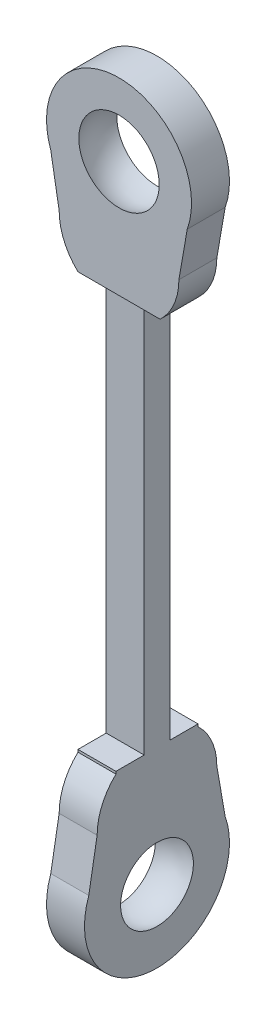
SolidWorks part; units mm, degrees
ref_plane "前视基准面" through (0, 0, 0) normal (0, 0, 1) x (1, 0, 0)
ref_plane "上视基准面" through (0, 0, 0) normal (0, 1, 0) x (1, 0, 0)
ref_plane "右视基准面" through (0, 0, 0) normal (1, 0, 0) x (0, 0, -1)
other "Configuration Table"
sketch "草图1" plane through (0, 0, 0) normal (0, 0, 1) x (1, 0, 0)
  circle A0 centre (0, 0) radius 2.165
  circle A1 centre (0, 0) radius 3.532
extrude "凸台-拉伸1" add sketch "草图1" along normal blind 2.849
sketch "草图3" plane through (0, 0, 2.849) normal (0, 0, 1) x (1, 0, 0)
  line L0 (-2.916, -3.532) -> (-3.532, 0)
  line L1 (2.916, -3.532) -> (3.532, 0)
  arc A0 (2.656, -2.3283) -> (3.3235, -1.1956) centre (0, 0) ccw
  arc A1 (-2.916, -3.532) -> (2.916, -3.532) centre (0, -3.532) ccw
  arc A2 (3.532, 0) -> (-3.532, 0) centre (0, 0) ccw
  circle M4 centre (0, 0) radius 3.532
extrude "凸台-拉伸3" add sketch "草图3" against normal up to surface (2.849 mm away) contours L0 A1 L1 M4 region at (0, -4.4115, 2.849) up to face at (3.532, 0, 0)
sketch "草图4" plane through (0, 0, 2.849) normal (0, 0, 1) x (1, 0, 0)
  line L0 (0, 0) -> (0, -15.25)
  line L1 (0, -6.448) -> (2, -6.448)
  line L2 (0, -6.448) -> (-2, -6.448)
  line L3 (-2, -6.448) -> (-2, -5.654)
  line L4 (2, -6.448) -> (2, -5.654)
  arc A0 (-2.916, -3.532) -> (2.916, -3.532) centre (0, -3.532) ccw construction
  arc A1 (-2, -5.654) -> (0, -6.448) centre (0, -3.532) ccw
  arc A2 (2, -5.654) -> (0, -6.448) centre (0, -3.532) cw
  arc M6 (-2.916, -3.532) -> (2.916, -3.532) centre (0, -3.532) ccw
extrude "凸台-拉伸4" add sketch "草图4" against normal up to surface (2.849 mm away) contours L1 L4 M6 | L2 L3 A1 region at (1.5146, -6.2166, 2.849) up to face at (0, -1.9109, 0)
sketch "草图5" plane through (0, 0, 2.849) normal (0, 0, 1) x (1, 0, 0)
  line L0 (-2, -6.448) -> (2, -6.448)
  line L1 (-2, -6.448) -> (-2, -15.25)
  line L2 (-2, -15.25) -> (2, -15.25)
  line L3 (2, -6.448) -> (2, -15.25)
extrude "凸台-拉伸5" add sketch "草图5" against normal up to surface (2.849 mm away) up to face at (0, -3.6401, 0)
ref_plane "基准面1" through (-12, 0, 0) normal (-1, 0, 0) x (0, 0, 1)
sketch "草图9" plane through (0, -15.25, 0) normal (0, -1, 0) x (1, 0, 0)
  circle A0 centre (0, 1.4245) radius 0.3861
ref_plane "基准面2" through (0, 0, 0) normal (-1, 0, 0) x (0, 0, 1)
sketch "草图11" plane through (0, 0, 0) normal (-1, 0, 0) x (0, 0, 1)
  line L0 (4.748, -29.3044) -> (4.3405, -26.968)
  line L1 (3.4245, -24.846) -> (3.4245, -15.25)
  line L2 (3.4245, -15.25) -> (-0.5755, -15.25)
  line L3 (-0.5755, -15.25) -> (-0.5755, -24.846)
  line L4 (-1.4915, -26.968) -> (-1.899, -29.3044)
  circle A0 centre (1.4245, -30.5) radius 2.165
  arc A1 (-1.899, -29.3044) -> (4.748, -29.3044) centre (1.4245, -30.5) ccw
  arc A2 (4.3405, -26.968) -> (3.4245, -24.846) centre (1.4245, -26.968) ccw
  arc A3 (-0.5755, -24.846) -> (-1.4915, -26.968) centre (1.4245, -26.968) ccw
extrude "凸台-拉伸6" add sketch "草图11" along normal blind 2 and the other way blind 2
sketch "草图12" plane through (-12, 0, 0) normal (-1, 0, 0) x (0, 0, 1)
  line L0 (0.5, 4.1241) -> (0.5, -15.2363)
  line L9 (0, -5.654) -> (0, -15.25) construction
  line L10 (0.5, -15.2363) -> (-0.8762, -15.2363)
  line L11 (-0.8762, -15.2363) -> (-0.8762, 4.1241)
  line L12 (-0.8762, 4.1241) -> (0.5, 4.1241)
  line L13 (2.349, 4.1241) -> (2.349, -15.2363)
  line L14 (2.349, -15.2363) -> (3.4441, -15.2363)
  line L15 (2.849, -15.25) -> (2.849, -5.654) construction
  line L16 (2.349, 4.1241) -> (3.4441, 4.1241)
  line L17 (3.4441, 4.1241) -> (3.4441, -15.2363)
  dimension "D1" = 0.5
  dimension "D2" = 0.5
extrude "切除-拉伸1" cut sketch "草图12" against normal blind 24
sketch "草图14" plane through (0, 0, 3.4245) normal (0, 0, 1) x (1, 0, 0)
  line L0 (-1.5, -15.25) -> (-1.5, -35.1595)
  line L1 (2, -15.25) -> (-2, -15.25) construction
  line L2 (-2, -24.846) -> (-2, -15.25) construction
  line L3 (-1.5, -15.25) -> (-3.435, -15.25)
  line L4 (-3.435, -15.25) -> (-3.435, -35.1595)
  line L5 (-3.435, -35.1595) -> (-1.5, -35.1595)
  line L6 (1.5, -15.25) -> (1.5, -35.1595)
  line L7 (2, -24.846) -> (2, -15.25) construction
  line L8 (1.5, -15.25) -> (3.4686, -15.25)
  line L9 (3.4686, -15.25) -> (3.4686, -35.1595)
  line L10 (3.4686, -35.1595) -> (1.5, -35.1595)
  dimension "D1" = 0.5
  dimension "D2" = 0.5
extrude "切除-拉伸2" cut sketch "草图14" against normal blind 24 and the other way blind 24
sketch "草图15" plane through (-12, 0, 0) normal (-1, 0, 0) x (0, 0, 1)
  line L0 (0.8, -5.654) -> (0.8, -24.7275)
  line L1 (0.5, -5.654) -> (2.349, -5.654) construction
  line L2 (0.8, -24.7275) -> (-1.8291, -24.7275)
  line L3 (-1.8291, -24.7275) -> (-1.8291, -5.654)
  line L4 (-1.8291, -5.654) -> (0.8, -5.654)
  line L5 (0.5, -5.654) -> (0.5, -15.2363) construction
  line L6 (2.049, -5.654) -> (2.049, -24.7275)
  line L7 (2.049, -24.7275) -> (5.2703, -24.7275)
  line L8 (5.2703, -24.7275) -> (5.2703, -5.654)
  line L9 (5.2703, -5.654) -> (2.049, -5.654)
  line L10 (2.349, -15.2363) -> (2.349, -5.654) construction
  dimension "D1" = 0.3
  dimension "D2" = 0.3
extrude "切除-拉伸3" cut sketch "草图15" against normal blind 24
sketch "草图16" plane through (0, 0, 0.8) normal (0, 0, -1) x (-1, 0, 0)
  line L0 (-1.5, -15.25) -> (-2, -15.25)
  line L1 (-2, -15.25) -> (-2, -5.654)
  line L2 (-2, -5.654) -> (-1.5, -5.654)
  line L3 (-2, -5.654) -> (2, -5.654) construction
  line L4 (-1.5, -5.654) -> (-1.5, -15.25)
  line L5 (1.5, -15.25) -> (1.5, -5.654)
  line L6 (1.5, -5.654) -> (2, -5.654)
  line L7 (2, -5.654) -> (2, -15.25)
  line L8 (2, -5.654) -> (2, -15.25) construction
  line L9 (1.5, -15.25) -> (2, -15.25) construction
  line L10 (2, -15.25) -> (1.5, -15.25)
extrude "切除-拉伸4" cut sketch "草图16" against normal blind 24
sketch "草图17" plane through (0, 0, 2.049) normal (0, 0, 1) x (1, 0, 0)
  line L0 (-0.925, -5.654) -> (-0.925, -35.9981)
  line L1 (-2, -5.654) -> (2, -5.654) construction
  line L2 (-1.5, -5.654) -> (-1.5, -24.7275) construction
  line L3 (-0.925, -5.654) -> (-2, -5.654)
  line L4 (-2, -5.654) -> (-2, -35.9981)
  line L5 (-2, -35.9981) -> (-0.925, -35.9981)
  line L6 (0.925, -5.654) -> (0.925, -35.9981)
  line L7 (1.5, -5.654) -> (-1.5, -5.654) construction
  line L8 (1.5, -24.7275) -> (1.5, -5.654) construction
  line L9 (0.925, -5.654) -> (2, -5.654)
  line L10 (2, -5.654) -> (2, -35.9981)
  line L11 (2, -35.9981) -> (0.925, -35.9981)
  dimension "D1" = 0.575
  dimension "D2" = 0.575
extrude "切除-拉伸5" cut sketch "草图17" against normal blind 24 and the other way blind 24
ref_plane "基准面3" through (0, 0, 1.4245) normal (0, 0, -1) x (-1, 0, 0)
sketch "草图18" plane through (0, 0, 1.4245) normal (0, 0, -1) x (-1, 0, 0)
  line L0 (0, 2.165) -> (0, -2.165)
  arc A0 (0, 2.165) -> (0, -2.165) centre (0, 0) ccw
sketch "草图19" plane through (0, 0, 0.5) normal (0, 0, -1) x (-1, 0, 0)
  circle A0 centre (0, 0) radius 2.165
extrude "凸台-拉伸7" add sketch "草图19" against normal up to surface (1.849 mm away) up to face at (0, 2.165, 2.349)
revolve "切除-旋转3" cut sketch "草图18" angle 360 about L0
ref_plane "基准面4" through (-0.925, 0, 0) normal (-1, 0, 0) x (0, 0, 1)
sketch "草图21" plane through (0.925, 0, 0) normal (1, 0, 0) x (0, 0, -1)
  circle A0 centre (-1.4245, -30.5) radius 2.165
extrude "凸台-拉伸9" add sketch "草图21" against normal up to surface (1.85 mm away) up to face at (-0.925, -23.0828, 1.4245)
sketch "草图22" plane through (0, 0, 0) normal (-1, 0, 0) x (0, 0, 1)
  line L1 (1.4245, -28.5) -> (1.4245, -32.5)
  arc A1 (1.4245, -28.5) -> (1.4245, -32.5) centre (1.4245, -30.5) ccw
revolve "切除-旋转4" cut sketch "草图22" angle 360 about L1
